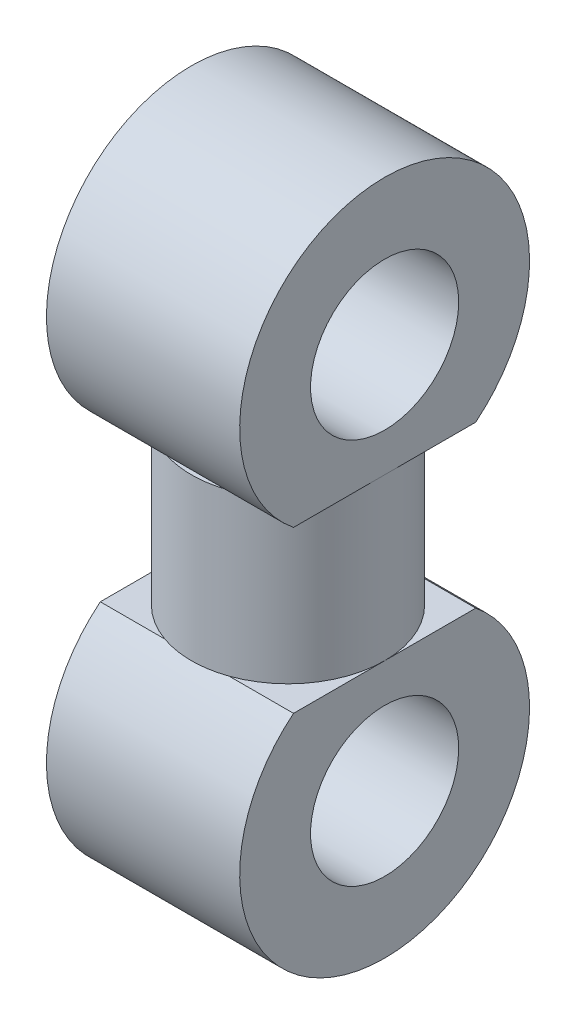
SolidWorks part; units mm, degrees
ref_plane "Front Plane" through (0, 0, 0) normal (0, 0, 1) x (1, 0, 0)
ref_plane "Top Plane" through (0, 0, 0) normal (0, 1, 0) x (1, 0, 0)
ref_plane "Right Plane" through (0, 0, 0) normal (1, 0, 0) x (0, 0, -1)
sketch "Sketch1" plane through (0, 0, 0) normal (0, 1, 0) x (1, 0, 0)
  circle A0 centre (0, 0) radius 3
  dimension "D1" = 6
extrude "crank_body" add sketch "Sketch1" along normal blind 4.5
sketch "Sketch2" plane through (0, 0, 0) normal (0, -1, 0) x (1, 0, 0)
  circle A0 centre (0, 0) radius 1.55
  dimension "D1" = 3.1
sketch "Sketch3" plane through (0, 0, 0) normal (1, 0, 0) x (0, 0, -1)
  line L0 (3, 4.5) -> (-3, 4.5) construction
  line L1 (-3, 4.5) -> (-3, 0) construction
  line L2 (-3, 4.5) -> (3, 4.5)
  line L3 (-3, 4.5) -> (-3, 5)
  line L4 (-3, 5) -> (3, 5)
  line L5 (3, 4.5) -> (3, 5)
  line L6 (3, 0) -> (3, 4.5) construction
  line L7 (-3, 4.5) -> (-3, 0) construction
  circle A0 centre (0, 8.5) radius 4.5
  dimension "D1" = 9
  dimension "D2" = 4
  dimension "D6" = 3
  dimension "D3" = 0.5
  dimension "D4" = 0
  dimension "D5" = 0
extrude "pin_shaft_body" add sketch "Sketch3" along normal blind 3 and the other way blind 3 contours A0 L3 L2 | L3 A0 L5 L4 | L5 A0 L3 L4 | L5 L4 L3 L2 region at (0, 4.6897, 2.6907) region at (0, 4.7628, 0) region at (0, 8.7525, 0)
sketch "Sketch4" plane through (3, 0, 0) normal (1, 0, 0) x (0, 0, -1)
  circle A0 centre (0, 8.5) radius 2.3
  dimension "D1" = 4.6
extrude "pin_shaft" cut sketch "Sketch4" against normal through all
extrude "smoothing_cuts" cut sketch "Sketch1<2>" along normal blind 5 flip side to cut
sketch "Sketch1<2>" plane through (0, 0, 0) normal (0, 1, 0) x (1, 0, 0) same geometry as "Sketch1"
ref_plane "Plane1" through (0, 2.5, 0) normal (0, -1, 0) x (-1, 0, 0)
mirror "Mirror1" about plane through (0, 2.5, 0) normal (0, -1, 0) of "smoothing_cuts", "pin_shaft_body", "pin_shaft"
